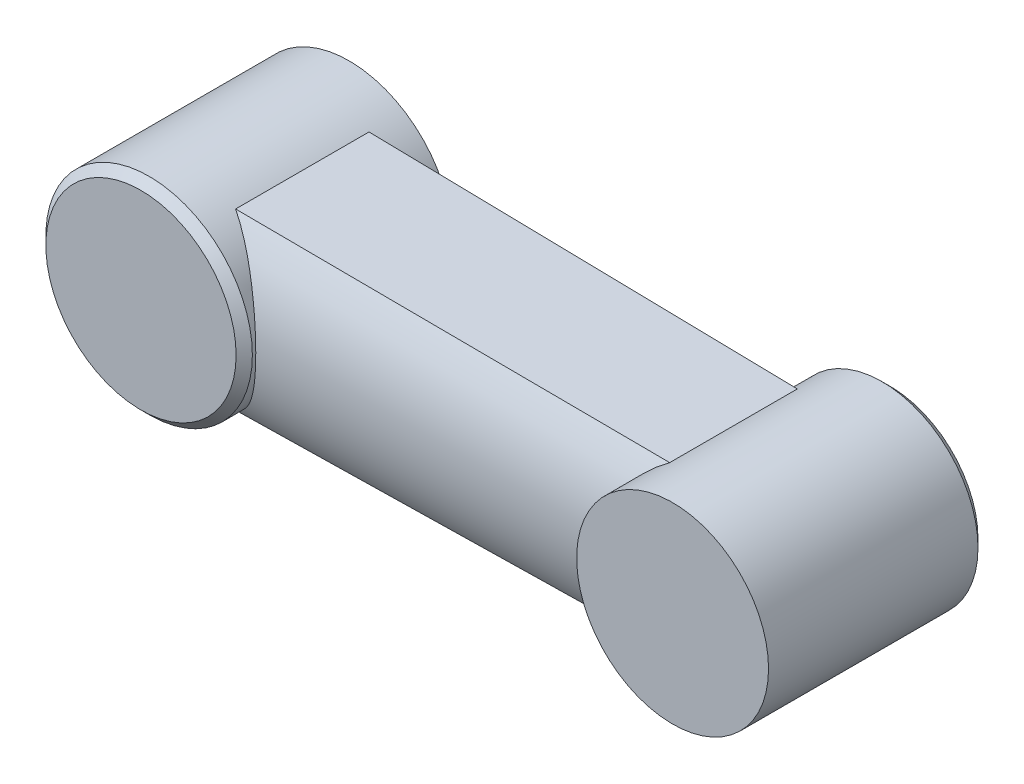
SolidWorks part; units mm, degrees
ref_plane "Front Plane" through (0, 0, 0) normal (0, 0, 1) x (1, 0, 0)
ref_plane "Top Plane" through (0, 0, 0) normal (0, 1, 0) x (1, 0, 0)
ref_plane "Right Plane" through (0, 0, 0) normal (1, 0, 0) x (0, 0, -1)
sketch "Sketch1" plane through (0, 0, 0) normal (0, 0, 1) x (1, 0, 0)
  circle A0 centre (0, 0) radius 63.5
  dimension "D1" = 127
extrude "Boss-Extrude1" add sketch "Sketch1" along normal blind 64 and the other way blind 64
chamfer "Chamfer1" distance 5 angle 45 1 edges at (63.5, 0, 64)
ref_plane "Plane2" through (63.5, 0, 0) normal (1, 0, 0) x (0, 0, -1)
ref_plane "Plane1" through (271.2, 0, 0) normal (1, 0, 0) x (0, 0, -1)
ref_plane "Plane3" through (330.2, 0, 0) normal (1, 0, 0) x (0, 0, -1)
ref_plane "Plane4" through (0, 0, 0) normal (0, 0, 1) x (1, 0, 0)
sketch "Sketch6" plane through (0, 0, 0) normal (-1, 0, 0) x (0, 0, 1)
  line L0 (-57.7088, 0) -> (57.7088, 0) construction
  line L6 (40.1204, -54) -> (-42.3796, -54)
  line L7 (-42.3796, 54) -> (40.1204, 54)
  arc A5 (-42.3796, 54) -> (-42.3796, -54) centre (45.0683, 0) ccw
  arc A6 (40.1204, 54) -> (40.1204, -54) centre (-33.9807, 0) cw
sketch "Sketch7" plane through (330.2, 0, 59) normal (-1, 0, 0) x (0, 0, 1)
  line L0 (-21.0035, -49.884) -> (-99.0528, -49.884)
  line L6 (-99.0528, 49.884) -> (-21.0035, 49.884)
  line L7 (-112.5928, 0) -> (-5.4072, 0) construction
  arc A9 (-99.0528, 49.884) -> (-99.0528, -49.884) centre (-13.9317, 0) ccw
  arc A10 (-21.0035, 49.884) -> (-21.0035, -49.884) centre (-92.9807, 0) cw
loft "Loft1" add profiles "Sketch6", "Sketch7" start constraint default end constraint default
sketch "Sketch9" plane through (0, 0, 0) normal (0, 0, 1) x (1, 0, 0)
  line L0 (330.2, -49.884) -> (330.2, 49.884) construction
  circle A0 centre (330.2, 0) radius 59
  dimension "D1" = 118
extrude "Boss-Extrude2" add sketch "Sketch9" along normal blind 67.3 and the other way blind 66.5
chamfer "Chamfer2" distance 5 angle 45 1 edges at (389.2, 0, -66.5)
ref_axis "Axis1" through (0, 0, 59) along (0, 0, -1)
ref_point "Point1"
